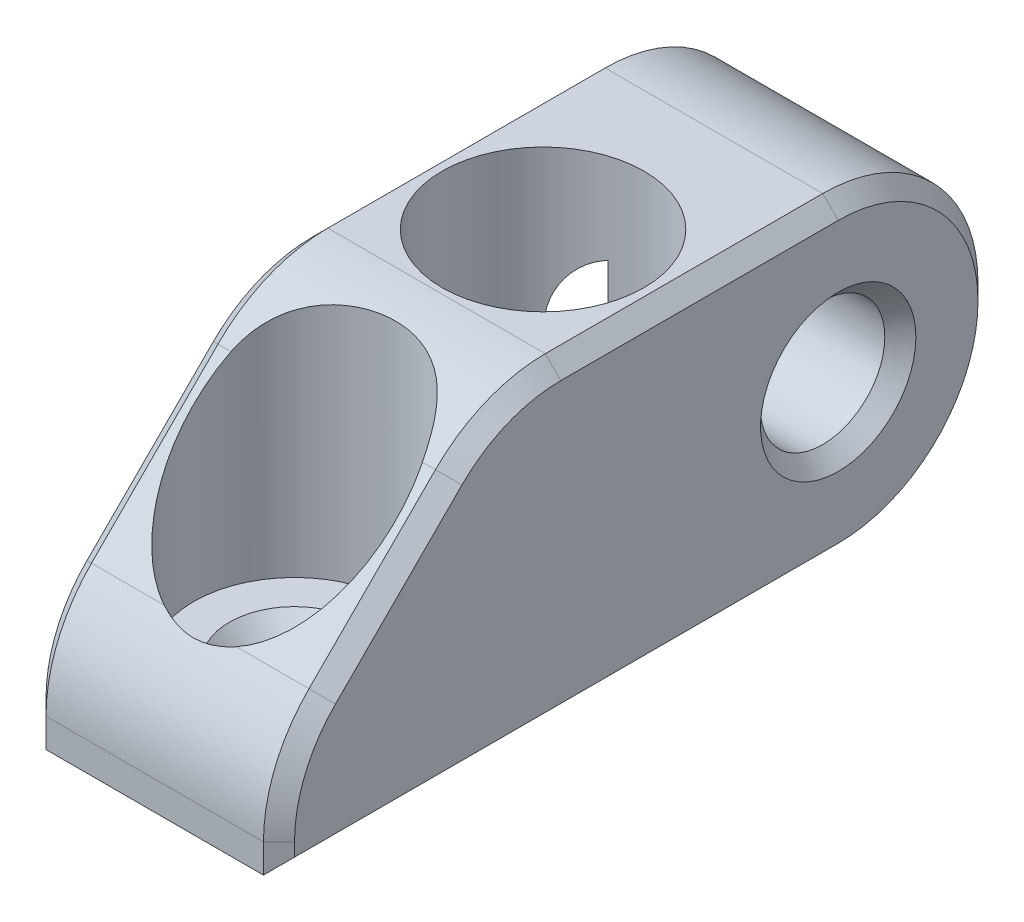
SolidWorks part; units mm, degrees
ref_plane "Front Plane" through (0, 0, 0) normal (0, 0, 1) x (1, 0, 0)
ref_plane "Top Plane" through (0, 0, 0) normal (0, 1, 0) x (1, 0, 0)
ref_plane "Right Plane" through (0, 0, 0) normal (1, 0, 0) x (0, 0, -1)
sketch "Sketch1" plane through (0, 0, 0) normal (0, 1, 0) x (1, 0, 0)
  line L0 (0, 0) -> (0, 1.27) construction
  line L1 (-5.08, -14.605) -> (5.08, -14.605)
  line L2 (-5.08, -14.605) -> (-5.08, 14.605)
  line L3 (-5.08, 14.605) -> (5.08, 14.605)
  line L4 (5.08, -14.605) -> (5.08, 14.605)
  line L5 (-5.08, -14.605) -> (5.08, 14.605) construction
  line L6 (-5.08, 14.605) -> (5.08, -14.605) construction
  line L7 (0, 0) -> (0, -8.89) construction
  circle A0 centre (0, 1.27) radius 2.032
  circle A1 centre (0, -8.89) radius 2.032
  circle A2 centre (0, 1.27) radius 4.1275
  circle A3 centre (0, -8.89) radius 4.1275
  point P0 (0, 0)
  dimension "D3" = 4.064
  dimension "D6" = 8.255
  dimension "D1" = 29.21
  dimension "D2" = 10.16
  dimension "D4" = 8.89
  dimension "D5" = 1.27
extrude "Boss-Extrude1" add sketch "Sketch1" along normal blind 12.7 contours L1 L4 L3 L2 A1 A0 | A1 | A0 | A2 A0 | A3 A1 region at (-4.7707, 0, 0) region at (0, 0, -1.27) region at (0, 0, 8.89) region at (-4.0108, 0, -1.27) region at (-4.0108, 0, 8.89)
extrude "Cut-Extrude2" cut sketch "Sketch1<3>" along normal through all contours A0 | A1 region at (0, 0, -1.27) region at (0, 0, 8.89)
sketch "Sketch1<3>" plane through (0, 0, 0) normal (0, 1, 0) x (1, 0, 0) same geometry as "Sketch1"
extrude "Cut-Extrude3" cut sketch "Sketch1<4>" against normal blind 10.16 from surface contours A3 A1 | A2 A0 region at (-4.0108, 0, -1.27) region at (-4.0108, 0, 8.89) starting at face at (0, 12.7, 0.762)
sketch "Sketch1<4>" plane through (0, 0, 0) normal (0, 1, 0) x (1, 0, 0) same geometry as "Sketch1"
sketch "Sketch2" plane through (-5.08, 0, 0) normal (-1, 0, 0) x (0, 0, 1)
  line L0 (-8.255, 0) -> (-8.255, 6.35) construction
  line L1 (14.605, 0) -> (-14.605, 0) construction
  circle A0 centre (-8.255, 6.35) radius 4.05
  dimension "D1" = 8.1
  dimension "D2" = 6.35
  dimension "D3" = 22.86
extrude "Cut-Extrude1" cut sketch "Sketch2" against normal blind 3.81 contours A0
sketch "Sketch3" plane through (-5.08, 0, 0) normal (-1, 0, 0) x (0, 0, 1)
  circle A0 centre (-8.255, 6.35) radius 4.05 construction
  circle A1 centre (-8.255, 6.35) radius 4.05
  circle A2 centre (-8.255, 6.35) radius 2.54
  dimension "D1" = 5.08
extrude "Cut-Extrude4" cut sketch "Sketch3" against normal through all contours A2
chamfer "Chamfer1" distance 8.89 angle 45 1 edges at (0, 12.7, 14.605)
fillet "Fillet1" radius 6.35 3 edges at (0, 3.81, 14.605) (-3.8587, 12.7, 5.715) (3.8587, 12.7, 5.715)
fillet "Fillet2" radius 6.35 2 edges at (0, 12.7, -14.605) (0, 0, -14.605)
chamfer "Chamfer2" distance 0.635 angle 45 23 edges at (-5.08, 6.35, -4.205) (5.08, 6.35, -5.715) (-1.27, 6.35, -5.715) (0, 2.54, 10.922) (0, 0, 10.922) (0, 0, 0.762) (0, 2.54, 0.762) (5.08, 0.5899, 14.605) (5.08, 3.6098, 14.1216) (5.08, 8.255, 10.16) (5.08, 12.2166, 5.5148) (5.08, 12.7, -2.5851) (5.08, 10.8401, -12.7451) (5.08, 1.8599, -12.7451) (5.08, 0, 3.175) (-5.08, 0.5899, 14.605) (-5.08, 3.6098, 14.1216) (-5.08, 8.255, 10.16) (-5.08, 12.2166, 5.5148) (-5.08, 12.7, -2.5851) (-5.08, 10.8401, -12.7451) (-5.08, 1.8599, -12.7451) (-5.08, 0, 3.175)
